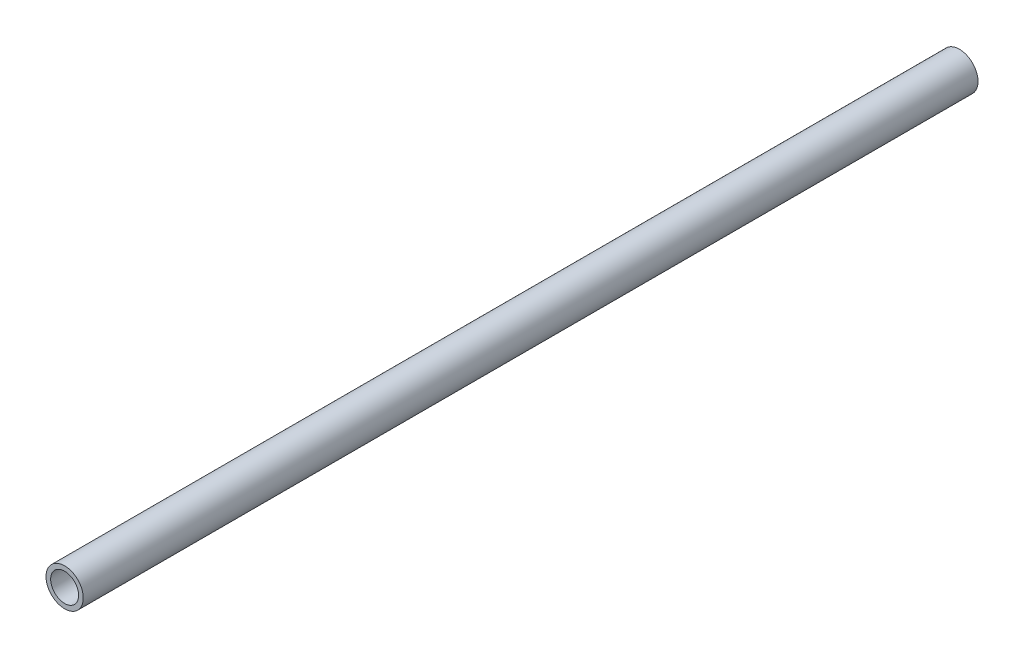
SolidWorks part; units mm, degrees
material "PC High Viscosity"
ref_plane "Front Plane" through (0, 0, 0) normal (0, 0, 1) x (1, 0, 0)
ref_plane "Top Plane" through (0, 0, 0) normal (0, 1, 0) x (1, 0, 0)
ref_plane "Right Plane" through (0, 0, 0) normal (1, 0, 0) x (0, 0, -1)
sketch "Sketch2" plane through (0, 0, 0) normal (0, 0, 1) x (1, 0, 0)
  circle A0 centre (0, 0) radius 9.525
  circle A1 centre (0, 0) radius 12.7
  dimension "D1" = 25.4
  dimension "D2" = 19.05
extrude "Boss-Extrude1" add sketch "Sketch2" along normal mid plane 609.6
